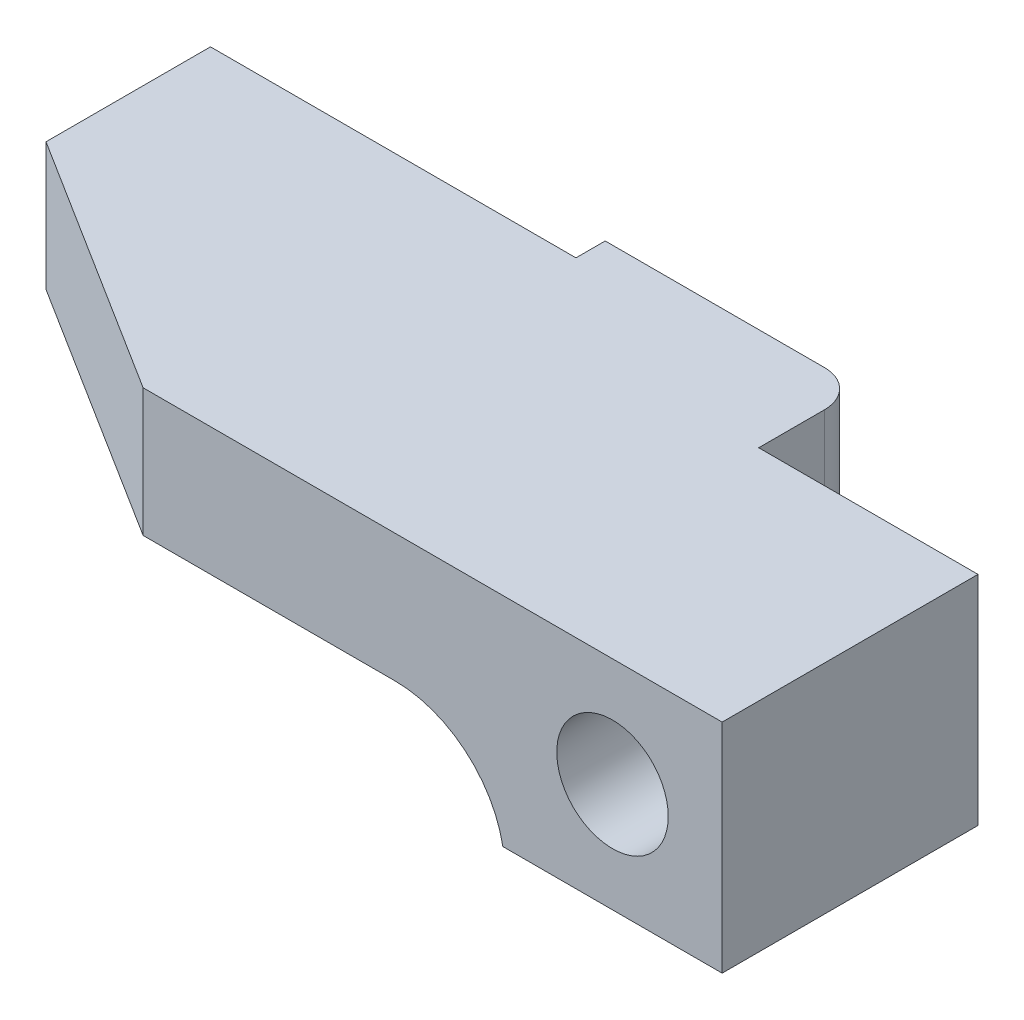
SolidWorks part; units mm, degrees
ref_plane "前视基准面" through (0, 0, 0) normal (0, 0, 1) x (1, 0, 0)
ref_plane "上视基准面" through (0, 0, 0) normal (0, 1, 0) x (1, 0, 0)
ref_plane "右视基准面" through (0, 0, 0) normal (1, 0, 0) x (0, 0, -1)
sketch "草图1" plane through (0, 0, 0) normal (0, 1, 0) x (1, 0, 0)
  line L1 (0, 0) -> (-6, 0)
  line L2 (0, 0) -> (0, 9)
  line L3 (0, 9) -> (-6, 9)
  line L4 (-6, 0) -> (-6, 9) construction
  line L6 (-13, 9) -> (-23, 9)
  line L9 (-13, 9) -> (-13, 9.8)
  line L10 (-13, 9.8) -> (-6, 9.8)
  line L11 (-6, 9.8) -> (-6, 9)
  line L12 (-15.8426, 0) -> (-6, 0)
  line L15 (-23, 9) -> (-23, 4.5)
  line L16 (-15.8426, 0) -> (-23, 4.5)
  dimension "D1" = 9
  dimension "D2" = 6
  dimension "D3" = 7
  dimension "D5" = 0.8
extrude "凸台-拉伸1" add sketch "草图1" along normal blind 3.5
sketch "草图3" plane through (0, 0, 0) normal (0, 1, 0) x (1, 0, 0)
  line L0 (-6, 9) -> (-6, 0)
  line L1 (-6, 0) -> (0, 0)
  line L9 (0, 0) -> (0, 9)
  line L10 (0, 9) -> (-6, 9)
  line L11 (-6, 9) -> (-6, 9.8)
  line L12 (-6, 9.8) -> (-13, 9.8)
  line L13 (-13, 9.8) -> (-13, 9)
  line L14 (-13, 9) -> (-23, 9)
  line L15 (-23, 9) -> (-23, 4.5)
  line L16 (-23, 4.5) -> (-15.8426, 0)
  line L17 (-15.8426, 0) -> (0, 0)
  line L18 (0, 0) -> (0, 9)
  line L19 (0, 9) -> (-6, 9)
  dimension "D1" = 0
extrude "凸台-拉伸2" add sketch "草图3" along normal blind 3.5 and the other way blind 2.45
sketch "草图4" plane through (0, 0, 0) normal (0, 1, 0) x (1, 0, 0)
  line L2 (0, 7) -> (0, 9)
  line L3 (0, 9) -> (-6, 9)
  line L4 (-6, 9) -> (-6, 9.8) construction
  line L5 (-6, 9) -> (-6, 7)
  line L6 (0, 7) -> (-6, 7)
extrude "切除-拉伸1" cut sketch "草图4" along normal through all and the other way through all
sketch "草图5" plane through (0, 0, 0) normal (0, 0, 1) x (1, 0, 0)
  line L0 (0, 0.525) -> (-3, 0.525) construction
  line L6 (-15.8426, 0) -> (-6, 0)
  line L7 (-6, 0) -> (-6, -2.45)
  line L8 (-6, -2.45) -> (0, -2.45)
  line L9 (0, -2.45) -> (0, 3.5)
  line L15 (0, 3.5) -> (-15.8426, 3.5)
  line L16 (-15.8426, 3.5) -> (-15.8426, 0)
  line L19 (-6, -2.45) -> (0, -2.45) construction
  line L20 (0, -2.45) -> (0, 3.5) construction
  circle A1 centre (-3, 0.525) radius 1.525
  dimension "D1" = 0
extrude "切除-拉伸2" cut sketch "草图5" against normal through all
fillet "圆角2" radius 1 1 edges at (-6, 1.75, -9.8)
fillet "圆角3" radius 3 1 edges at (-6, 0, -3.5)
